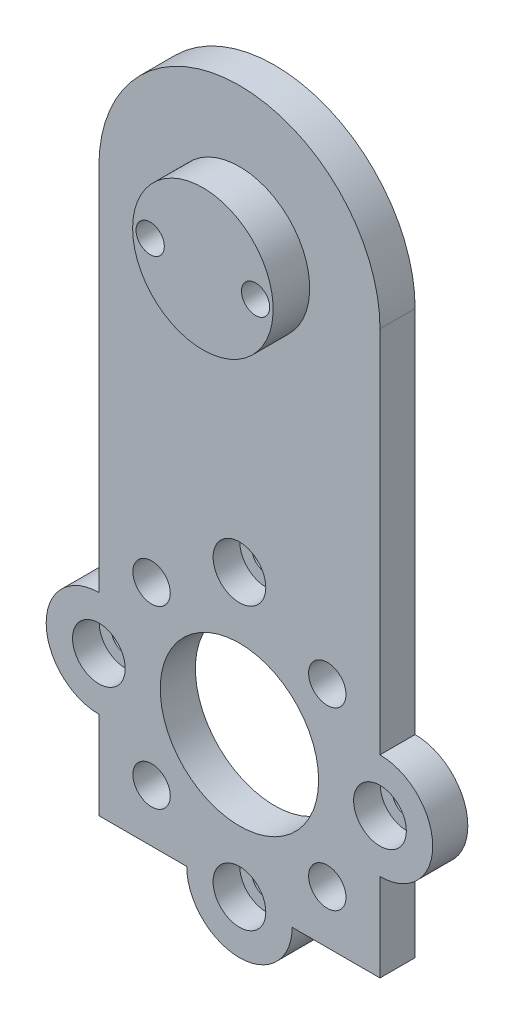
SolidWorks part; units mm, degrees
material "6061 Alloy"
ref_plane "Front Plane" through (0, 0, 0) normal (0, 0, 1) x (1, 0, 0)
ref_plane "Top Plane" through (0, 0, 0) normal (0, 1, 0) x (1, 0, 0)
ref_plane "Right Plane" through (0, 0, 0) normal (1, 0, 0) x (0, 0, -1)
sketch "Sketch1" plane through (0, 0, 0) normal (0, 0, 1) x (1, 0, 0)
  line L1 (0, 0) -> (15.875, 0)
  line L6 (-9.525, 25.4) -> (60.325, 25.4) construction
  line L7 (25.4, -9.525) -> (25.4, 25.4) construction
  line L14 (0, 0) -> (0, 15.875)
  line L15 (50.8, 101.6) -> (50.8, 34.925)
  line L16 (0, 34.925) -> (0, 101.6)
  line L17 (50.8, 15.875) -> (50.8, 0)
  line L18 (34.925, 0) -> (50.8, 0)
  arc A0 (50.8, 101.6) -> (0, 101.6) centre (25.4, 101.6) ccw
  circle A4 centre (41.275, 9.525) radius 3.3782
  circle A5 centre (9.525, 9.525) radius 3.3782
  circle A6 centre (9.525, 41.275) radius 3.3782
  circle A7 centre (41.275, 41.275) radius 3.3782
  arc A8 (50.8, 15.875) -> (50.8, 34.925) centre (50.8, 25.4) ccw
  arc A9 (0, 15.875) -> (0, 34.925) centre (0, 25.4) cw
  arc A10 (34.925, 0) -> (15.875, 0) centre (25.4, 0) cw
  circle A11 centre (25.4, 25.4) radius 14.3129
  dimension "D1" = 101.6
  dimension "D7" = 6.7564
  dimension "D8" = 9.525
  dimension "D9" = 15.875
  dimension "D11" = 25.4
  dimension "D12" = 28.6258
  dimension "D2" = 31.75
  dimension "D3" = 9.525
  dimension "D4" = 31.75
  dimension "D5" = 50.8
  dimension "D6" = 9.525
  dimension "D10" = 15.875
extrude "Boss-Extrude1" add sketch "Sketch1" along normal blind 6.35
sketch "Sketch2" plane through (0, 0, 6.35) normal (0, 0, 1) x (1, 0, 0)
  line L0 (0, 101.6) -> (50.8, 101.6) construction
  line L1 (25.4, 127) -> (25.4, 101.6) construction
  arc A0 (50.8, 101.6) -> (0, 101.6) centre (25.4, 101.6) ccw construction
  circle A1 centre (25.4, 101.6) radius 12.7
  dimension "D1" = 25.4
extrude "Boss-Extrude2" add sketch "Sketch2" along normal blind 6.604
hole_wizard "CBORE for #10 Socket Head Cap Screw1" positions "Sketch3" profile "Sketch4" counterbore size "#10" standard "ANSI Inch" end condition through all
sketch "Sketch3" plane through (0, 0, 6.35) normal (0, 0, 1) x (1, 0, 0)
  line L0 (34.925, 0) -> (50.8, 0) construction
  circle A0 centre (25.4, 25.4) radius 25.4 construction
  point P0 (0, 25.4)
  point P3 (50.8, 25.4)
  point P6 (25.4, 0)
  point P14 (25.4, 50.8)
  dimension "D1" = 50.8
  dimension "D2" = 25.4
sketch "Sketch4" plane through (0, 25.4, 6.35) normal (1, 0, 0) x (0, -1, 0)
  line L0 (0, 0) -> (0, 6.35)
  line L1 (0, 6.35) -> (2.5527, 6.35)
  line L3 (2.5527, 6.35) -> (2.5527, 4.826)
  line L4 (2.5527, 4.826) -> (4.7625, 4.826)
  line L5 (4.7625, 4.826) -> (4.7625, 0)
  line L7 (4.7625, 0) -> (0, 0)
  line L11 (0, -6.35) -> (0, 107.95) construction
  dimension "Thru Hole Dia." = 5.1054
  dimension "Thru Hole Depth" = 6.35
  dimension "C'Bore Dia." = 9.525
  dimension "C'Bore Depth" = 4.826
hole_wizard "1/4-20 Tapped Hole2" positions "Sketch8" profile "Sketch9" tap size "1/4-20" standard "ANSI Inch" end condition through all
sketch "Sketch8" plane through (0, 0, 12.954) normal (0, 0, 1) x (1, 0, 0)
  line L0 (12.7, 101.6) -> (38.1, 101.6) construction
  line L2 (25.4, 114.3) -> (25.4, 88.9) construction
  circle A0 centre (25.4, 101.6) radius 12.7 construction
  circle A1 centre (25.4, 101.6) radius 12.7 construction
  point P0 (15.875, 101.6)
  point P2 (34.925, 101.6)
  dimension "D1" = 19.05
  dimension "D2" = 3.175
  dimension "D3" = 3.175
sketch "Sketch9" plane through (15.875, 101.6, 12.954) normal (1, 0, 0) x (0, -1, 0)
  line L0 (0, 0) -> (0, 12.954)
  line L1 (0, 12.954) -> (2.5527, 12.954)
  line L2 (2.5527, 12.954) -> (2.5527, 0)
  line L5 (2.5527, 0) -> (0, 0)
  line L11 (0, -6.35) -> (0, 107.95) construction
  dimension "Thru Tap Drill Dia." = 5.1054
  dimension "Thru Tap Drill Depth" = 12.954
cosmetic thread "Hole Thread3" parameters "D2"=6.35
cosmetic thread "Hole Thread4" parameters "D2"=6.35
